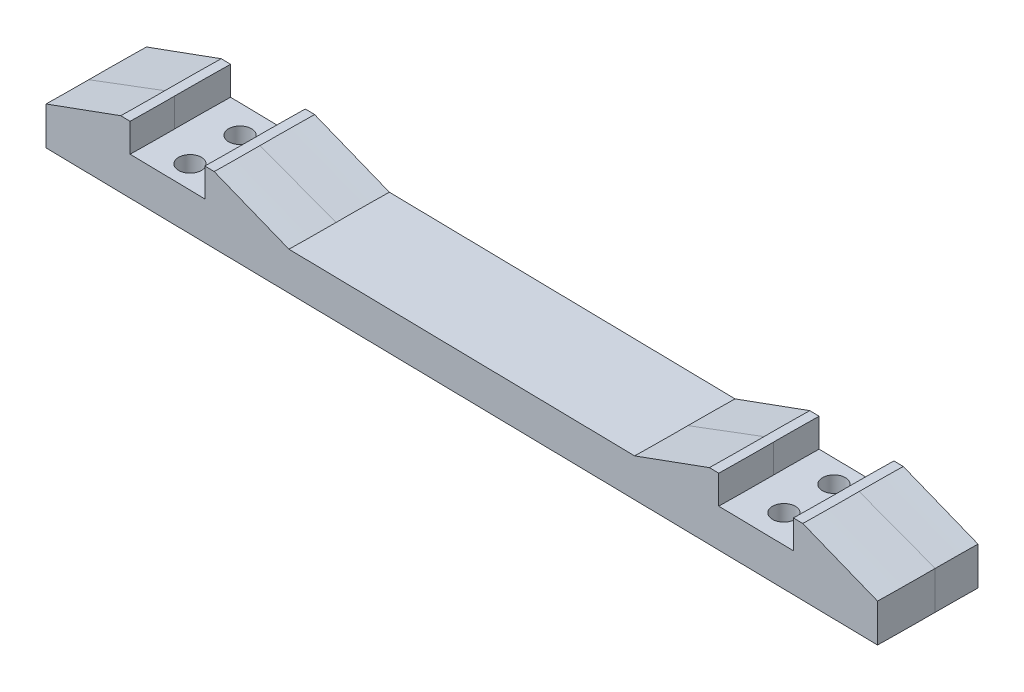
SolidWorks part; units mm, degrees
other "标注1"
sketch "草图3" plane through (-22.25, 4, -10) normal (-0.231, 0.6469, -0.7268) x (-0.9696, -0.2151, 0.1167)
ref_plane "前视基准面" through (0, 0, 0) normal (0, 0, 1) x (1, 0, 0)
ref_plane "上视基准面" through (0, 0, 0) normal (0, 1, 0) x (1, 0, 0)
ref_plane "右视基准面" through (0, 0, 0) normal (1, 0, 0) x (0, 0, -1)
other "Configuration Table"
sketch "草图4" plane through (0, 0, 0) normal (0, 0, 1) x (1, 0, 0)
  line L6 (8.5, -1.5) -> (17.75, -1.5)
  line L11 (17.75, -1.5) -> (17.75, -3.5)
  line L16 (17.75, -3.5) -> (-4.5, -3.5)
  line L17 (-4.5, -3.5) -> (-4.5, -1.5)
  line L19 (0, 0) -> (0, -1.5)
  line L20 (0, -1.5) -> (4, -1.5)
  line L21 (4, -1.5) -> (4, 0)
  line L26 (4, 0) -> (4.5, 0)
  line L27 (4.5, 0) -> (8.5, -1.5)
  line L28 (0, 0) -> (-0.5, 0)
  line L29 (-0.5, 0) -> (-4.5, -1.5)
  dimension "D2" = 4
  dimension "D4" = 0.5
  dimension "D5" = 2
  dimension "D6" = 2
  dimension "D7" = 4
  dimension "D8" = 1.5
  dimension "D9" = 4
  dimension "D10" = 22.25
extrude "凸台-拉伸1" add sketch "草图4" along normal blind 2.5 contours L28 L29 L17 L16 L11 L6 L27 L26 L21 L20 L19 | L19 | L21 region at (5.9579, -2.2764, 0)
sketch "草图5" plane through (0, -1.5, 0) normal (0, 1, 0) x (1, 0, 0)
  line L0 (0, 0) -> (4, -2.5) construction
  line L1 (0, -2.5) -> (0, 0) construction
  line L2 (0, -2.5) -> (4, -2.5) construction
  line L3 (4, -2.5) -> (4, 0) construction
  line L4 (0, 0) -> (4, 0) construction
  circle A0 centre (2, -1.25) radius 0.6
  circle A1 centre (2, -1.25) radius 1
  dimension "D1" = 1.2
  dimension "D2" = 2
extrude "切除-拉伸1" cut sketch "草图5" against normal through all contours A0
extrude "切除-拉伸2" cut sketch "草图5<3>" along normal blind 1 from surface contours A1 starting at face at (2, -3.5, 1.85)
sketch "草图5<3>" plane through (0, -1.5, 0) normal (0, 1, 0) x (1, 0, 0) same geometry as "草图5"
mirror "镜向1" about plane through (17.75, 0, 2.5) normal (1, 0, 0) of bodies 215
sketch "草图6" plane through (0, 0, 2.5) normal (0, 0, 1) x (1, 0, 0)
  line L18 (0, 0) -> (-0.5, 0)
  line L19 (-0.5, 0) -> (-4.5, -1.5)
  line L20 (-4.5, -1.5) -> (-4.5, -3.5)
  line L21 (-4.5, -3.5) -> (40, -3.5)
  line L22 (40, -3.5) -> (40, -1.5)
  line L23 (40, -1.5) -> (36, 0)
  line L24 (36, 0) -> (35.5, 0)
  line L25 (35.5, 0) -> (35.5, -1.5)
  line L26 (35.5, -1.5) -> (31.5, -1.5)
  line L27 (31.5, -1.5) -> (31.5, 0)
  line L28 (31.5, 0) -> (31, 0)
  line L29 (31, 0) -> (27, -1.5)
  line L30 (27, -1.5) -> (8.5, -1.5)
  line L31 (8.5, -1.5) -> (4.5, 0)
  line L32 (4.5, 0) -> (4, 0)
  line L33 (4, 0) -> (4, -1.5)
  line L34 (4, -1.5) -> (0, -1.5)
  line L35 (0, -1.5) -> (0, 0)
  line L36 (0, 0) -> (-0.5, 0)
  line L37 (-0.5, 0) -> (-4.5, -1.5)
  line L38 (-4.5, -1.5) -> (-4.5, -3.5)
  line L39 (-4.5, -3.5) -> (40, -3.5)
  line L40 (40, -3.5) -> (40, -1.5)
  line L41 (40, -1.5) -> (36, 0)
  line L42 (36, 0) -> (35.5, 0)
  line L43 (35.5, 0) -> (35.5, -1.5)
  line L44 (35.5, -1.5) -> (31.5, -1.5)
  line L45 (31.5, -1.5) -> (31.5, 0)
  line L46 (31.5, 0) -> (31, 0)
  line L47 (31, 0) -> (27, -1.5)
  line L48 (27, -1.5) -> (8.5, -1.5)
  line L49 (8.5, -1.5) -> (4.5, 0)
  line L50 (4.5, 0) -> (4, 0)
  line L51 (4, 0) -> (4, -1.5)
  line L52 (4, -1.5) -> (0, -1.5)
  line L53 (0, -1.5) -> (0, 0)
  dimension "D1" = 0
sketch "草图8" plane through (0, 0, 2.5) normal (0, 0, 1) x (1, 0, 0)
  line L0 (-132.25, 94.8536) -> (-132.25, -34.2886)
  line L1 (17.75, -1.5) -> (17.75, -3.5)
  line L2 (27, -1.5) -> (8.5, -1.5) construction
  line L3 (-4.5, -3.5) -> (40, -3.5) construction
  dimension "D1" = 150
revolve "旋转1" add sketch "草图6" angle 1 about L0
sketch "草图9" plane through (0, -1.5, 0) normal (0, 1, 0) x (1, 0, 0)
  line L0 (-0.005, -3.6541) -> (3.9948, -3.689) construction
  line L1 (3.9948, -3.689) -> (31.4938, -3.929) construction
  line L2 (31.4938, -3.929) -> (35.4936, -3.9639) construction
  arc A0 (-0.0201, -4.8081) -> (0, -2.5) centre (-132.25, -2.5) ccw construction
  arc A1 (3.9792, -4.8779) -> (4, -2.5) centre (-132.25, -2.5) ccw construction
  arc A2 (31.4751, -5.3578) -> (31.5, -2.5) centre (-132.25, -2.5) ccw construction
  arc A3 (35.4745, -5.4276) -> (35.5, -2.5) centre (-132.25, -2.5) ccw construction
  circle A4 centre (1.9949, -3.6715) radius 1
  circle A5 centre (1.9949, -3.6715) radius 0.6
  circle A6 centre (33.4937, -3.9464) radius 1
  circle A7 centre (33.4937, -3.9464) radius 0.6
  dimension "D1" = 2
  dimension "D2" = 1.2
extrude "切除-拉伸3" cut sketch "草图9" against normal through all contours A7 | A5
extrude "切除-拉伸4" cut sketch "草图9<3>" along normal blind 1 from surface contours A6 | A4 starting at face at (32.8937, -3.5, 3.9464)
sketch "草图9<3>" plane through (0, -1.5, 0) normal (0, 1, 0) x (1, 0, 0) same geometry as "草图9"
sketch "草图10" plane through (0, 0, 0) normal (0, 1, 0) x (1, 0, 0)
  line L1 (40, -2.5) -> (-4.5, -2.5)
  line L2 (40, -2.5) -> (40, 0)
  line L3 (40, 0) -> (-4.5, 0)
  line L4 (-4.5, -2.5) -> (-4.5, 0)
extrude "切除-拉伸5" cut sketch "草图10" against normal through all
sketch "草图11" plane through (0, 0, 2.5) normal (0, 0, -1) x (-1, 0, 0)
  line L18 (0.5, 0) -> (0, 0)
  line L19 (0, 0) -> (0, -1.5)
  line L20 (0, -1.5) -> (-4, -1.5)
  line L21 (-4, -1.5) -> (-4, 0)
  line L22 (-4, 0) -> (-4.5, 0)
  line L23 (-4.5, 0) -> (-8.5, -1.5)
  line L24 (-8.5, -1.5) -> (-27, -1.5)
  line L25 (-27, -1.5) -> (-31, 0)
  line L26 (-31, 0) -> (-31.5, 0)
  line L27 (-31.5, 0) -> (-31.5, -1.5)
  line L28 (-31.5, -1.5) -> (-35.5, -1.5)
  line L29 (-35.5, -1.5) -> (-35.5, 0)
  line L30 (-35.5, 0) -> (-36, 0)
  line L31 (-36, 0) -> (-40, -1.5)
  line L32 (-40, -1.5) -> (-40, -3.5)
  line L33 (-40, -3.5) -> (4.5, -3.5)
  line L34 (4.5, -3.5) -> (4.5, -1.5)
  line L35 (4.5, -1.5) -> (0.5, 0)
  line L36 (0.5, 0) -> (0, 0)
  line L37 (0, 0) -> (0, -1.5)
  line L38 (0, -1.5) -> (-4, -1.5)
  line L39 (-4, -1.5) -> (-4, 0)
  line L40 (-4, 0) -> (-4.5, 0)
  line L41 (-4.5, 0) -> (-8.5, -1.5)
  line L42 (-8.5, -1.5) -> (-27, -1.5)
  line L43 (-27, -1.5) -> (-31, 0)
  line L44 (-31, 0) -> (-31.5, 0)
  line L45 (-31.5, 0) -> (-31.5, -1.5)
  line L46 (-31.5, -1.5) -> (-35.5, -1.5)
  line L47 (-35.5, -1.5) -> (-35.5, 0)
  line L48 (-35.5, 0) -> (-36, 0)
  line L49 (-36, 0) -> (-40, -1.5)
  line L50 (-40, -1.5) -> (-40, -3.5)
  line L51 (-40, -3.5) -> (4.5, -3.5)
  line L52 (4.5, -3.5) -> (4.5, -1.5)
  line L53 (4.5, -1.5) -> (0.5, 0)
  dimension "D1" = 0
sketch "草图13" plane through (0, 0, 2.5) normal (0, 0, -1) x (-1, 0, 0)
  line L0 (-167.75, 63.0117) -> (-167.75, -22.7585)
  line L1 (-17.75, -1.5) -> (-17.75, -3.5) construction
  point P4 (-17.75, -2.5)
  dimension "D1" = 150
revolve "旋转2" add sketch "草图11" angle 1 about L0
sketch "草图14" plane through (0, -1.5, 0) normal (0, 1, 0) x (1, 0, 0)
  line L0 (0.0064, -1.0361) -> (4.0062, -1.071) construction
  line L1 (4.0062, -1.071) -> (31.5052, -1.311) construction
  line L2 (31.5052, -1.311) -> (35.505, -1.3459) construction
  arc A0 (0.0255, 0.4276) -> (0, -2.5) centre (167.75, -2.5) ccw construction
  arc A1 (4.0249, 0.3578) -> (4, -2.5) centre (167.75, -2.5) ccw construction
  arc A4 (31.5208, -0.1221) -> (31.5, -2.5) centre (167.75, -2.5) ccw construction
  arc A5 (35.5201, -0.1919) -> (35.5, -2.5) centre (167.75, -2.5) ccw construction
  circle A6 centre (2.0063, -1.0536) radius 1
  circle A7 centre (2.0063, -1.0536) radius 0.6
  circle A8 centre (33.5051, -1.3285) radius 1
  circle A9 centre (33.5051, -1.3285) radius 0.6
  circle A10 centre (33.4937, -3.9464) radius 0.6 construction
  circle A11 centre (1.9949, -3.6715) radius 1 construction
extrude "切除-拉伸6" cut sketch "草图14" against normal through all contours A9 | A7
extrude "切除-拉伸7" cut sketch "草图14<3>" along normal blind 1 from surface contours A6 | A8 starting at face at (32.9051, -3.5, 1.3285)
sketch "草图14<3>" plane through (0, -1.5, 0) normal (0, 1, 0) x (1, 0, 0) same geometry as "草图14"
